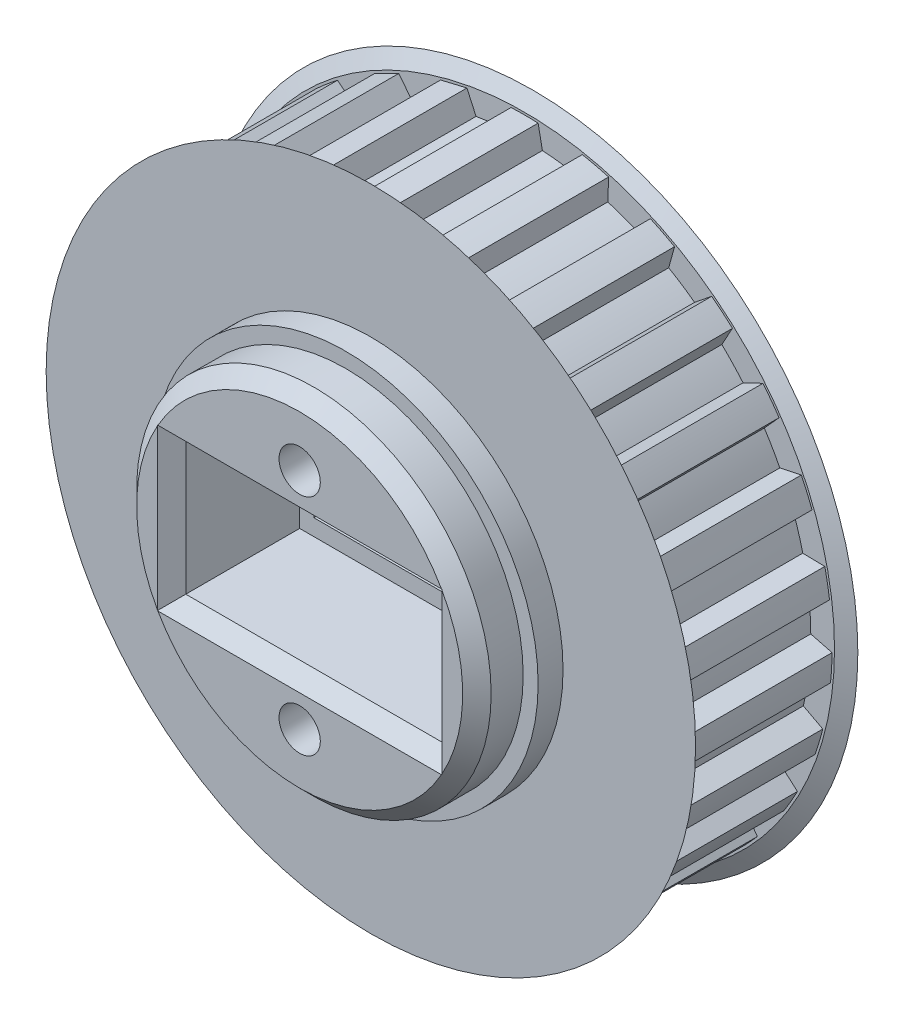
SolidWorks part; units mm, degrees
material "ABS"
ref_plane "Alzado" through (0, 0, 0) normal (0, 0, 1) x (1, 0, 0)
ref_plane "Planta" through (0, 0, 0) normal (0, 1, 0) x (1, 0, 0)
ref_plane "Vista lateral" through (0, 0, 0) normal (1, 0, 0) x (0, 0, -1)
sketch "Croquis1" plane through (0, 0, 0) normal (0, 0, 1) x (1, 0, 0)
  line L0 (0, 0) -> (0, 14.5885) construction
  line L1 (-0.95, 21.5791) -> (-1.25, 20.0611)
  line L2 (0.95, 21.5791) -> (1.25, 20.0611)
  line L3 (5.9009, 20.7783) -> (5.8427, 19.2321)
  line L4 (4.0521, 21.2165) -> (3.4101, 19.8086)
  line L5 (10.5336, 18.8574) -> (10.1204, 17.3662)
  line L6 (8.8357, 19.7101) -> (7.8864, 18.4882)
  line L7 (14.5985, 15.9199) -> (13.8526, 14.5642)
  line L8 (13.143, 17.1412) -> (11.9375, 16.1712)
  line L9 (17.8764, 12.1241) -> (16.8379, 10.977)
  line L10 (16.7418, 13.6482) -> (15.345, 12.9823)
  line L11 (20.1906, 7.6747) -> (18.9155, 6.798)
  line L12 (19.438, 9.4193) -> (17.9253, 9.0936)
  line L13 (21.4162, 2.8116) -> (19.9734, 2.2526)
  line L14 (21.0863, 4.6827) -> (19.5393, 4.7146)
  line L15 (21.4874, -2.2031) -> (19.9545, -2.4143)
  line L16 (21.5978, -0.3063) -> (20.0998, 0.0814)
  line L17 (20.4001, -7.099) -> (18.8598, -6.9511)
  line L18 (20.945, -5.2789) -> (19.5768, -4.5561)
  line L19 (18.213, -11.6123) -> (16.7484, -11.1131)
  line L20 (19.163, -9.9668) -> (17.9984, -8.948)
  line L21 (15.0441, -15.4995) -> (13.7341, -14.676)
  line L22 (16.348, -14.1175) -> (15.4497, -12.8575)
  line L23 (11.0642, -18.5511) -> (9.9794, -17.4477)
  line L24 (12.6516, -17.507) -> (12.0681, -16.0739)
  line L25 (6.4878, -20.6026) -> (5.6867, -19.2788)
  line L26 (8.2732, -19.9528) -> (8.0359, -18.4237)
  line L27 (1.5616, -21.5435) -> (1.0874, -20.0706)
  line L28 (3.4488, -21.3229) -> (3.5705, -19.7803)
  line L29 (-3.4488, -21.3229) -> (-3.5705, -19.7803)
  line L30 (-1.5616, -21.5435) -> (-1.0874, -20.0706)
  line L31 (-8.2732, -19.9528) -> (-8.0359, -18.4237)
  line L32 (-6.4878, -20.6026) -> (-5.6867, -19.2788)
  line L33 (-12.6516, -17.507) -> (-12.0681, -16.0739)
  line L34 (-11.0642, -18.5511) -> (-9.9794, -17.4477)
  line L35 (-16.348, -14.1175) -> (-15.4497, -12.8575)
  line L36 (-15.0441, -15.4995) -> (-13.7341, -14.676)
  line L37 (-19.163, -9.9668) -> (-17.9984, -8.948)
  line L38 (-18.213, -11.6123) -> (-16.7484, -11.1131)
  line L39 (-20.945, -5.2789) -> (-19.5768, -4.5561)
  line L40 (-20.4001, -7.099) -> (-18.8598, -6.9511)
  line L41 (-21.5978, -0.3063) -> (-20.0998, 0.0814)
  line L42 (-21.4874, -2.2031) -> (-19.9545, -2.4143)
  line L43 (-21.0863, 4.6827) -> (-19.5393, 4.7146)
  line L44 (-21.4162, 2.8116) -> (-19.9734, 2.2526)
  line L45 (-19.438, 9.4193) -> (-17.9253, 9.0936)
  line L46 (-20.1906, 7.6747) -> (-18.9155, 6.798)
  line L47 (-16.7418, 13.6482) -> (-15.345, 12.9823)
  line L48 (-17.8764, 12.1241) -> (-16.8379, 10.977)
  line L49 (-13.143, 17.1412) -> (-11.9375, 16.1712)
  line L50 (-14.5985, 15.9199) -> (-13.8526, 14.5642)
  line L51 (-8.8357, 19.7101) -> (-7.8864, 18.4882)
  line L52 (-10.5336, 18.8574) -> (-10.1204, 17.3662)
  line L53 (-10.5336, 18.8574) -> (-8.8357, 19.7101)
  line L54 (-4.0521, 21.2165) -> (-3.4101, 19.8086)
  line L55 (-5.9009, 20.7783) -> (-5.8427, 19.2321)
  line L56 (-5.9009, 20.7783) -> (-4.0521, 21.2165)
  arc A0 (-10.1204, 17.3662) -> (-11.9375, 16.1712) centre (0, 0) ccw
  arc A1 (3.4101, 19.8086) -> (1.25, 20.0611) centre (0, 0) ccw
  arc A2 (-5.8427, 19.2321) -> (-7.8864, 18.4882) centre (0, 0) ccw
  arc A9 (-13.143, 17.1412) -> (-14.5985, 15.9199) centre (0, 0) ccw
  arc A10 (-16.7418, 13.6482) -> (-17.8764, 12.1241) centre (0, 0) ccw
  arc A11 (5.9009, 20.7783) -> (4.0521, 21.2165) centre (0, 0) ccw
  arc A12 (0.95, 21.5791) -> (-0.95, 21.5791) centre (0, 0) ccw
  arc A16 (10.5336, 18.8574) -> (8.8357, 19.7101) centre (0, 0) ccw
  arc A17 (14.5985, 15.9199) -> (13.143, 17.1412) centre (0, 0) ccw
  arc A18 (17.8764, 12.1241) -> (16.7418, 13.6482) centre (0, 0) ccw
  arc A19 (20.1906, 7.6747) -> (19.438, 9.4193) centre (0, 0) ccw
  arc A20 (21.4162, 2.8116) -> (21.0863, 4.6827) centre (0, 0) ccw
  arc A21 (21.4874, -2.2031) -> (21.5978, -0.3063) centre (0, 0) ccw
  arc A22 (20.4001, -7.099) -> (20.945, -5.2789) centre (0, 0) ccw
  arc A23 (18.213, -11.6123) -> (19.163, -9.9668) centre (0, 0) ccw
  arc A24 (15.0441, -15.4995) -> (16.348, -14.1175) centre (0, 0) ccw
  arc A25 (11.0642, -18.5511) -> (12.6516, -17.507) centre (0, 0) ccw
  arc A26 (-8.2732, -19.9528) -> (-6.4878, -20.6026) centre (0, 0) ccw
  arc A27 (-12.6516, -17.507) -> (-11.0642, -18.5511) centre (0, 0) ccw
  arc A28 (-16.348, -14.1175) -> (-15.0441, -15.4995) centre (0, 0) ccw
  arc A29 (-20.945, -5.2789) -> (-20.4001, -7.099) centre (0, 0) ccw
  arc A30 (-21.5978, -0.3063) -> (-21.4874, -2.2031) centre (0, 0) ccw
  arc A31 (-21.0863, 4.6827) -> (-21.4162, 2.8116) centre (0, 0) ccw
  arc A32 (-19.438, 9.4193) -> (-20.1906, 7.6747) centre (0, 0) ccw
  arc A33 (-3.4488, -21.3229) -> (-1.5616, -21.5435) centre (0, 0) ccw
  arc A34 (1.5616, -21.5435) -> (3.4488, -21.3229) centre (0, 0) ccw
  arc A35 (6.4878, -20.6026) -> (8.2732, -19.9528) centre (0, 0) ccw
  arc A36 (7.8864, 18.4882) -> (5.8427, 19.2321) centre (0, 0) ccw
  arc A37 (11.9375, 16.1712) -> (10.1204, 17.3662) centre (0, 0) ccw
  arc A39 (-1.25, 20.0611) -> (-3.4101, 19.8086) centre (0, 0) ccw
  arc A43 (15.345, 12.9823) -> (13.8526, 14.5642) centre (0, 0) ccw
  arc A44 (17.9253, 9.0936) -> (16.8379, 10.977) centre (0, 0) ccw
  arc A45 (19.5393, 4.7146) -> (18.9155, 6.798) centre (0, 0) ccw
  arc A46 (20.0998, 0.0814) -> (19.9734, 2.2526) centre (0, 0) ccw
  arc A47 (19.5768, -4.5561) -> (19.9545, -2.4143) centre (0, 0) ccw
  arc A48 (17.9984, -8.948) -> (18.8598, -6.9511) centre (0, 0) ccw
  arc A49 (15.4497, -12.8575) -> (16.7484, -11.1131) centre (0, 0) ccw
  arc A50 (12.0681, -16.0739) -> (13.7341, -14.676) centre (0, 0) ccw
  arc A51 (8.0359, -18.4237) -> (9.9794, -17.4477) centre (0, 0) ccw
  arc A52 (3.5705, -19.7803) -> (5.6867, -19.2788) centre (0, 0) ccw
  arc A53 (-1.0874, -20.0706) -> (1.0874, -20.0706) centre (0, 0) ccw
  arc A54 (-5.6867, -19.2788) -> (-3.5705, -19.7803) centre (0, 0) ccw
  arc A55 (-9.9794, -17.4477) -> (-8.0359, -18.4237) centre (0, 0) ccw
  arc A56 (-13.7341, -14.676) -> (-12.0681, -16.0739) centre (0, 0) ccw
  arc A57 (-16.7484, -11.1131) -> (-15.4497, -12.8575) centre (0, 0) ccw
  arc A58 (-18.8598, -6.9511) -> (-17.9984, -8.948) centre (0, 0) ccw
  arc A59 (-19.9545, -2.4143) -> (-19.5768, -4.5561) centre (0, 0) ccw
  arc A60 (-19.9734, 2.2526) -> (-20.0998, 0.0814) centre (0, 0) ccw
  arc A61 (-18.9155, 6.798) -> (-19.5393, 4.7146) centre (0, 0) ccw
  arc A62 (-16.8379, 10.977) -> (-17.9253, 9.0936) centre (0, 0) ccw
  arc A63 (-13.8526, 14.5642) -> (-15.345, 12.9823) centre (0, 0) ccw
  arc A71 (-19.163, -9.9668) -> (-18.213, -11.6123) centre (0, 0) ccw
  circle A72 centre (0, 0) radius 1.5
  point P151 (0, 0)
  dimension "D1" = 21.6
  dimension "D6" = 3
  dimension "D5" = 1.5
  dimension "D2" = 2.5
  dimension "D3" = 1.9
  dimension "D4" = 27
extrude "Saliente-Extruir1" add sketch "Croquis1" along normal blind 10.2
sketch "Croquis2" plane through (0, 0, 10.2) normal (0, 0, 1) x (1, 0, 0)
  circle A0 centre (0, 0) radius 23.5
  circle A1 centre (0, 0) radius 1.5
  circle A2 centre (0, 0) radius 1.5 construction
  dimension "D1" = 47
extrude "Saliente-Extruir2" add sketch "Croquis2" along normal blind 0.6
sketch "Croquis3" plane through (0, 0, 10.8) normal (0, 0, 1) x (1, 0, 0)
  circle A0 centre (0, 0) radius 1.5
  circle A1 centre (0, 0) radius 12.45
  circle A3 centre (0, 0) radius 1.5 construction
  dimension "D1" = 24.9
sketch "Croquis4" plane through (0, 0, 0) normal (0, 0, -1) x (-1, 0, 0)
  circle A0 centre (0, 0) radius 1.5
  circle A1 centre (0, 0) radius 12.45
  circle A2 centre (0, 0) radius 1.5 construction
  dimension "D1" = 24.9
extrude "Saliente-Extruir4" add sketch "Croquis4" along normal blind 4.25
sketch "Croquis6" plane through (0, 0, 0) normal (0, 0, -1) x (-1, 0, 0)
  circle A0 centre (0, 0) radius 23.5
  circle A1 centre (0, 0) radius 1.5
  circle A2 centre (0, 0) radius 1.5 construction
  dimension "D1" = 47
extrude "Saliente-Extruir6" add sketch "Croquis6" along normal blind 0.6
sketch "Croquis5" plane through (0, 0, -0.6) normal (0, 0, -1) x (-1, 0, 0)
  circle A0 centre (0, 0) radius 1.5
  circle A1 centre (0, 0) radius 13.5
  circle A2 centre (0, 0) radius 1.5 construction
  dimension "D1" = 27
extrude "Saliente-Extruir5" add sketch "Croquis5" along normal blind 1.75
chamfer "Chaflán2" distance 1 angle 60 2 edges at (-23.5, 0, 0) (23.5, 0, 10.2)
extrude "Saliente-Extruir7" add sketch "Croquis3" along normal blind 5
chamfer "Chaflán4" distance 1 angle 45 1 edges at (12.45, 0, 15.8)
sketch "Croquis7" plane through (0, 0, 10.8) normal (0, 0, 1) x (1, 0, 0)
  circle A0 centre (0, 0) radius 1.5
  circle A1 centre (0, 0) radius 13.5
  circle A2 centre (0, 0) radius 1.5 construction
  dimension "D1" = 27
extrude "Saliente-Extruir8" add sketch "Croquis7" along normal blind 1.75
sketch "Croquis8" plane through (0, 0, 0) normal (0, 0, 1) x (1, 0, 0)
  line L0 (0, 0) -> (6.706, 0) construction
  line L1 (-8, 3.5) -> (8, 3.5)
  line L2 (-8, 3.5) -> (-8, -3.5)
  line L3 (-8, -3.5) -> (8, -3.5)
  line L4 (8, 3.5) -> (8, -3.5)
  line L5 (-8, 3.5) -> (8, -3.5) construction
  line L6 (-8, -3.5) -> (8, 3.5) construction
  circle A0 centre (0, 7.8756) radius 1.45
  circle A1 centre (0, -7.8756) radius 1.45
  point P0 (0, 0)
  dimension "D1" = 2.9
  dimension "D2" = 7
  dimension "D3" = 16
extrude "Cortar-Extruir1" cut sketch "Croquis8" against normal through all both and the other way through all
sketch "Croquis10" plane through (0, 0, 15.8) normal (0, 0, 1) x (1, 0, 0)
  line L1 (9, 4.65) -> (-9, 4.65)
  line L2 (9, 4.65) -> (9, -4.65)
  line L3 (9, -4.65) -> (-9, -4.65)
  line L4 (-9, 4.65) -> (-9, -4.65)
  line L5 (9, 4.65) -> (-9, -4.65) construction
  line L6 (9, -4.65) -> (-9, 4.65) construction
  point P0 (0, 0)
  dimension "D1" = 9.3
  dimension "D2" = 18
extrude "Cortar-Extruir3" cut sketch "Croquis10" against normal blind 9
chamfer "Chaflán5" distance 1 angle 45 8 edges at (-8, 0, -4.25) (0, 3.5, -4.25) (8, 0, -4.25) (0, -3.5, -4.25) (9, 0, 15.8) (0, 4.65, 15.8) (-9, 0, 15.8) (0, -4.65, 15.8)
sketch "Sketch1" plane through (0, 0, -4.25) normal (0, 0, -1) x (-1, 0, 0)
  circle A0 centre (0, 0) radius 12.45
  circle A1 centre (0, 0) radius 12.45 construction
  circle A2 centre (0, 7.8756) radius 1.45
  circle A3 centre (0, -7.8756) radius 1.45
  circle A4 centre (0, 7.8756) radius 1.45 construction
extrude "Boss-Extrude1" add sketch "Sketch1" against normal blind 5
sketch "Sketch2" plane through (0, 0, -4.25) normal (0, 0, -1) x (-1, 0, 0)
  line L0 (0, 17.274) -> (0, -20.0751) construction
  line L1 (-7.5, 0) -> (7.5, 0) construction
  circle A0 centre (-7.5, 0) radius 1.45
  circle A1 centre (7.5, 0) radius 1.45
  dimension "D1" = 2.9
  dimension "D2" = 15
extrude "Cut-Extrude1" cut sketch "Sketch2" against normal through all
sketch "Sketch4" plane through (0, 0, 15.8) normal (0, 0, 1) x (1, 0, 0)
  line L0 (-8, -3.5) -> (8, -3.5) construction
  line L1 (4, 3.5) -> (-4, 3.5)
  line L2 (4, 3.5) -> (4, -3.5)
  line L3 (4, -3.5) -> (-4, -3.5)
  line L4 (-4, 3.5) -> (-4, -3.5)
  line L5 (4, 3.5) -> (-4, -3.5) construction
  line L6 (4, -3.5) -> (-4, 3.5) construction
  point P0 (0, 0)
  dimension "D1" = 8
extrude "Cut-Extrude2" cut sketch "Sketch4" against normal blind 21
chamfer "Chamfer3" distance 1 angle 45 4 edges at (-4, 0, -4.25) (0, 3.5, -4.25) (4, 0, -4.25) (0, -3.5, -4.25)
chamfer "Chamfer2" distance 0.75 angle 45 1 edges at (-12.45, 0, -4.25)
